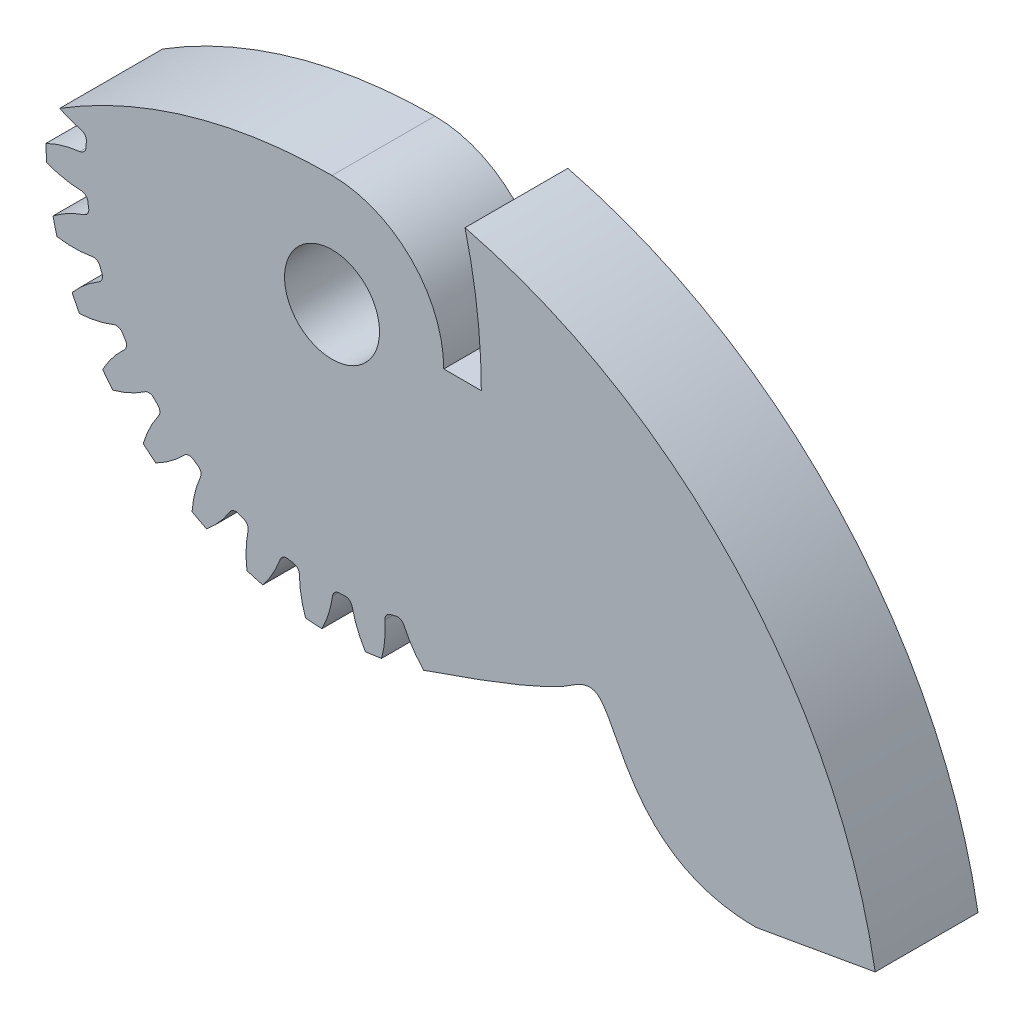
SolidWorks part; units mm, degrees
material "ABS"
ref_plane "Front" through (0, 0, 0) normal (0, 0, 1) x (1, 0, 0)
ref_plane "Top" through (0, 0, 0) normal (0, 1, 0) x (1, 0, 0)
ref_plane "Right" through (0, 0, 0) normal (1, 0, 0) x (0, 0, -1)
sketch "Sketch3" plane through (0, 0, 0) normal (0, 0, 1) x (1, 0, 0)
  circle A0 centre (0, 0) radius 40.64
  dimension "od" = 81.28
extrude "gearBody" add sketch "Sketch3" along normal blind 14.605
sketch "Sketch2" plane through (0, 0, 0) normal (0, 0, 1) x (1, 0, 0)
  line L0 (0, 0) -> (34.0786, 14.1158) construction
  line L1 (45.4751, -11.4855) -> (0, 0) construction
  line L2 (0, 0) -> (36.3143, 0) construction
  line L3 (38.0972, -0.458) -> (37.8451, -4.4001) construction
  line L5 (37.9712, -2.4291) -> (0, 0) construction
  line L7 (0, 0) -> (36.8864, 0) construction
  arc A0 (36.879, -0.7403) -> (36.6727, -3.9649) centre (0, 0) ccw construction
  arc A1 (40.637, 0.4947) -> (40.2427, -5.6687) centre (0, 0) ccw construction
  arc A2 (38.0972, -0.458) -> (37.8451, -4.4001) centre (0, 0) ccw construction
  arc A3 (34.9015, -2.6404) -> (34.9534, -1.8283) centre (0, 0) ccw
  arc A4 (45.4751, -11.4855) -> (35.6466, -3.6712) centre (32.0022, -18.3431) ccw
  arc A5 (45.4751, -11.4855) -> (46.5679, 5.5974) centre (0, 0) ccw
  arc A6 (46.5679, 5.5974) -> (35.8238, -0.9008) centre (34.0786, 14.1158) cw
  arc A7 (34.9534, -1.8283) -> (35.8238, -0.9008) centre (35.9376, -1.8798) cw
  arc A8 (35.6466, -3.6712) -> (34.9015, -2.6404) centre (35.8842, -2.7147) cw
  point P6 (46.5679, 5.5974)
  point P22 (45.4751, -11.4855)
  dimension "baseDia" = 73.7729
  dimension "od" = 81.28
  dimension "pd" = 76.2
  dimension "rd" = 70.0024
  dimension "rFillet" = 0.9855
  dimension "pointX" = 46.5679
  dimension "pointY" = 5.5974
  dimension "CTT" = 3.9421
  dimension "flankCenterAngle" = 22.5
extrude "toothCut" cut sketch "Sketch2" along normal through all
pattern_circular "CirPattern1" count 30 over 360 about axis through (0, 0, 14.605) along (0, 0, -1) of "toothCut"
sketch "hub1Dia" plane through (0, 0, 0) normal (0, 0, -1) x (-1, 0, 0)
  circle A0 centre (0, 0) radius 12.7
  dimension "hub1Dia" = 25.4
sketch "hub2Dia" plane through (0, 0, 14.605) normal (0, 0, 1) x (1, 0, 0)
  circle A0 centre (0, 0) radius 12.7
  dimension "hub2dia" = 25.4
sketch "boreDia" plane through (0, 0, 0) normal (0, 0, 1) x (1, 0, 0)
  circle A0 centre (0, 0) radius 6.7469
  dimension "boreDia" = 13.4937
extrude "bore" cut sketch "boreDia" against normal mid plane 25400
sketch "Sketch4" plane through (0, 0, 14.605) normal (0, 0, 1) x (1, 0, 0)
  circle A0 centre (0, -57.15) radius 78.359
  arc A2 (-42.9159, 8.4119) -> (42.9159, 8.4119) centre (0, 0) cw
  dimension "D1" = 156.718
  dimension "D2" = 57.15
extrude "Cut-Extrude1" cut sketch "Sketch4" against normal through all contours A0 region at (0, 27.8712, 14.605)
sketch "Sketch5" plane through (0, 0, 14.605) normal (0, 0, 1) x (1, 0, 0)
  line L0 (0, 21.209) -> (21.5163, 5.902)
  line L1 (21.5163, 5.902) -> (8.9608, -26.928)
  line L2 (8.9608, -26.928) -> (13.028, -38.4952)
  line L3 (0, 0) -> (0, -57.15) construction
  line L4 (0, -57.15) -> (-55.7146, -2.05) construction
  line L5 (0, -57.15) -> (67.8609, -96.3295) construction
  line L9 (0, -57.15) -> (77.1686, -43.5431) construction
  line L12 (60.232, -46.5295) -> (77.1686, -43.5431)
  line L13 (0, -57.15) -> (39.5947, -34.29) construction
  line L14 (39.5947, -34.29) -> (36.4197, -28.7907) construction
  circle A1 centre (0, -57.15) radius 78.359 construction
  arc A5 (0, 21.209) -> (77.1686, -43.5431) centre (0, -57.15) cw
  circle A6 centre (0, -57.15) radius 21.59 construction
  circle A12 centre (49.4934, -85.725) radius 40.64 construction
  spline S0 degree 3 poles (13.028, -38.4952) (34.3641, -31.2172) (33.2674, -29.3092) (40.5997, -27.9667) (42.6261, -46.4877) (60.232, -46.5295) knots 0 0 0 0 0.394503 0.494503 1 1 1 1
  point P28 (21.569, -56.1981)
  dimension "D1" = 43.18
  dimension "D3" = 81.28
  dimension "D6" = 156.718
  dimension "D2" = 120
  dimension "D4" = 57.15
  dimension "D8" = 57.15
  dimension "D7" = 60
  dimension "D9" = 45.72
  dimension "D10" = 6.35
  dimension "D5" = 80
extrude "Boss-Extrude1" add sketch "Sketch5" against normal up to surface (14.605 mm away) up to face at (6.7469, 0, 0)
sketch "Sketch6" plane through (0, 0, 14.605) normal (0, 0, 1) x (1, 0, 0)
  line L1 (-41.2993, 3.0747) -> (-43.5539, 7.9898)
  line L2 (15.875, 0) -> (21.209, 0)
  circle A0 centre (0, -57.15) radius 78.359 construction
  arc A1 (77.1686, -43.5431) -> (-36.286, 12.3011) centre (0, -57.15) ccw construction
  circle A2 centre (0, 0) radius 15.875 construction
  arc A3 (0, 15.875) -> (15.875, 0) centre (0, 0) cw
  arc A4 (18.8964, 18.8964) -> (-43.5539, 7.9898) centre (0, -57.15) ccw
  arc A5 (0, 15.875) -> (-41.2993, 3.0747) centre (0, -57.15) ccw
  circle A6 centre (0, 0) radius 21.209 construction
  circle A8 centre (-57.15, 0) radius 78.359 construction
  arc A9 (21.209, 0) -> (18.8964, 18.8964) centre (-57.15, 0) ccw
  dimension "D4" = 57.15
  dimension "D1" = 31.75
  dimension "D2" = 42.418
  dimension "D3" = 156.718
extrude "Cut-Extrude2" cut sketch "Sketch6" against normal through all
equation "\"Bodytube_OD\" = 6.17in"
equation "\"Bodytube_ID\" = 5.998in"
equation "\"Fwd_Tube_Length\" = 40in"
equation "\"Mid_Tube_Length\" = 1in"
equation "\"Aft_Section_Length\"= 39in"
equation "\"Mid_Coupler_Length\"= 13in"
equation "\"Aft_Lower_Length\"= 22in"
equation "\"AB_Coupler_OD_Length\"= 1in"
equation "\"AB_Coupling_Section_Length\"= 0.375in"
equation "\"AB_Coupler_Length\"= \"AB_Coupler_OD_Length\" + \"AB_Coupling_Section_Length\" * 2"
equation "\"Cutout_Angle\" = 80"
equation "\"AB_Paddle_Height\" = 0.575in"
equation "\"AB_Coupler_Num_Screws\"= 6"
equation "\"Num_Cutouts\" = 3"
equation "\"AB_Coupler_OD\"= 6.17in"
equation "\"AB_Coupler_ID\"= 5.75in"
equation "\"AB_Coupler_Surface_Diameter\"= 5.998in"
equation "\"AB_Coupling_Screw_Diameter\"= 0.1065in"
equation "\"AB_Central_Bushing_Length\" = .75in"
equation "\"Lead_Screw_Dist\" = 2.25in"
equation "\"Lead_Screw_Diam\" = 11mm"
equation "\"Lead_Screw_Length\" = (\"Mid_Coupler_Length\" + 2*0.375in + 2*0.5in)"
equation "\"Paddle_Pin_Offset\" = .25in"
equation "\"Paddle_Pin_Radius\" = 2.25in"
equation "\"Fwd_BKHD_From_Top\" = 18in"
equation "\"D1@Sketch4\"=\"Bodytube_OD\""
equation "\"D2@Sketch4\"=\"Paddle_Pin_Radius\""
equation "\"D3@Sketch5\"=\"Paddle_Gear_OD\""
equation "\"D4@Sketch5\"=\"Paddle_Pin_Radius\""
equation "\"Motor_OD\" = 4in"
equation "\"Aft_Upper_Length\"= \"Aft_Section_Length\" - \"Aft_Lower_Length\" - \"AB_Coupler_OD_Length\""
equation "\"Paddle_Gear_OD\" = 3.2in"
equation "\"D5@Sketch5\"=\"Cutout_Angle\""
equation "\"D6@Sketch5\"=\"Bodytube_OD\""
equation "\"D1@Sketch6\"=\"AB_Coupler_ID\"-2*\"Paddle_Pin_Radius\""
equation "\"D2@Sketch6\"=\"Bodytube_OD\"-2*\"Paddle_Pin_Radius\""
equation "\"D3@Sketch6\"=\"Bodytube_OD\""
equation "\"D4@Sketch6\"=\"Paddle_Pin_Radius\""
equation "\"D8@Sketch5\"=\"Paddle_Pin_Radius\""
equation "\"Drive_Gear_OD\" = 1.7in"
equation "\"Fin_Thickness\"= .118in"
equation "\"Guiderail_Cutout_Diameter\"= 1.5in"
equation "\"DB9_Hole_Dist\" = 25mm"
equation "\"D1@Sketch5\"=\"Drive_Gear_OD\""
